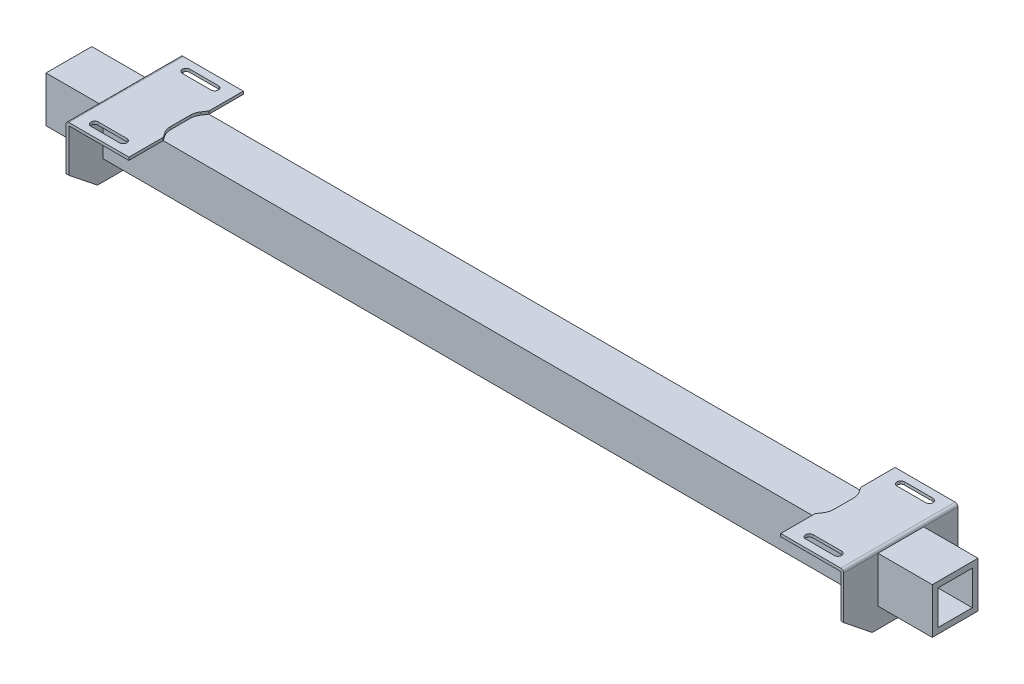
SolidWorks part; units mm, degrees
ref_plane "Front Plane" through (0, 0, 0) normal (0, 0, 1) x (1, 0, 0)
ref_plane "Top Plane" through (0, 0, 0) normal (0, 1, 0) x (1, 0, 0)
ref_plane "Right Plane" through (0, 0, 0) normal (1, 0, 0) x (0, 0, -1)
sketch "Sketch3" plane through (0, 0, 0) normal (1, 0, 0) x (0, 0, -1)
  line L1 (0, 0) -> (80, 0)
  line L2 (0, 0) -> (0, 80)
  line L3 (0, 80) -> (80, 80)
  line L4 (80, 0) -> (80, 80)
  line L5 (10, 70) -> (70, 70)
  line L6 (10, 70) -> (10, 10)
  line L7 (10, 10) -> (70, 10)
  line L8 (70, 70) -> (70, 10)
  dimension "D1" = 80
  dimension "D2" = 80
  dimension "D3" = 10
  dimension "D4" = 10
  dimension "D5" = 10
  dimension "D6" = 10
extrude "Boss-Extrude2" add sketch "Sketch3" along normal blind 1550
ref_plane "Plane1" through (1450, 0, 0) normal (1, 0, 0) x (0, 0, -1)
sketch "Sketch7" plane through (1450, 0, 0) normal (1, 0, 0) x (0, 0, -1)
  line L0 (-60, 85) -> (140, 85)
  line L1 (140, 85) -> (140, 5)
  line L2 (140, 5) -> (90, -35)
  line L3 (90, -35) -> (-10, -35)
  line L4 (-10, -35) -> (-60, 5)
  line L5 (-60, 5) -> (-60, 85)
  line L6 (80, 80) -> (0, 80) construction
  line L7 (70, 70) -> (10, 70) construction
  line L8 (70, 70) -> (10, 70)
  line L9 (70, 10) -> (70, 70) construction
  line L10 (10, 10) -> (70, 10) construction
  line L11 (10, 70) -> (10, 10) construction
  line L12 (70, 10) -> (70, 70)
  line L13 (10, 10) -> (70, 10)
  line L14 (10, 70) -> (10, 10)
  point P10 (40, 85)
  point P11 (40, 80)
  dimension "D1" = 200
  dimension "D2" = 120
  dimension "D3" = 50
  dimension "D4" = 50
  dimension "D5" = 5
  dimension "D6" = 40
extrude "Boss-Extrude3" add sketch "Sketch7" along normal blind 5
sketch "Sketch8" plane through (0, 0, -80) normal (0, 0, -1) x (-1, 0, 0)
  line L0 (-1455, 85) -> (-1450, 85) construction
  line L1 (-1455, 85) -> (-1345, 85)
  line L2 (-1455, 85) -> (-1455, 80)
  line L3 (-1455, 80) -> (-1345, 80)
  line L4 (-1345, 85) -> (-1345, 80)
  line L5 (-1455, 5) -> (-1455, 85) construction
  dimension "D1" = 5
  dimension "D2" = 110
extrude "Boss-Extrude4" add sketch "Sketch8" along normal up to surface and the other way up to surface up to face at (1452.5, 45, -140) other way up to face at (1452.5, 45, 60)
sketch "Sketch9" plane through (0, 85, 0) normal (0, 1, 0) x (1, 0, 0)
  line L0 (1345, 80) -> (1350.8013, 71.2981)
  line L1 (1345, 140) -> (1345, -60) construction
  line L2 (1355, 57.4306) -> (1355, 22.5694)
  line L3 (1350.8013, 8.7019) -> (1345, 0)
  line L4 (1345, 0) -> (0, 0) construction
  line L5 (1345, 0) -> (1345, 80)
  line L6 (1550, 80) -> (1550, 0) construction
  arc A0 (1355, 22.5694) -> (1350.8013, 8.7019) centre (1330, 22.5694) cw
  arc A1 (1350.8013, 71.2981) -> (1355, 57.4306) centre (1330, 57.4306) cw
  point P15 (1355, 15)
  point P18 (1355, 65)
  dimension "D4" = 25
  dimension "D1" = 10
  dimension "D2" = 15
  dimension "D3" = 15
extrude "Cut-Extrude1" cut sketch "Sketch9" against normal up to surface (5 mm away) up to face at (1397.5, 80, 30)
sketch "Sketch10" plane through (0, 85, 0) normal (0, 1, 0) x (1, 0, 0)
  line L0 (1375, 120) -> (1425, 120) construction
  line L1 (1375, 126.5) -> (1425, 126.5)
  line L2 (1375, 113.5) -> (1425, 113.5)
  line L3 (1375, -40) -> (1425, -40) construction
  line L4 (1375, -33.5) -> (1425, -33.5)
  line L5 (1375, -46.5) -> (1425, -46.5)
  line L6 (1455, 140) -> (1345, 140) construction
  arc A0 (1375, 126.5) -> (1375, 113.5) centre (1375, 120) ccw
  arc A1 (1425, 113.5) -> (1425, 126.5) centre (1425, 120) ccw
  arc A2 (1375, -33.5) -> (1375, -46.5) centre (1375, -40) ccw
  arc A3 (1425, -46.5) -> (1425, -33.5) centre (1425, -40) ccw
  point P2 (1400, 120)
  point P7 (1400, -40)
  point P16 (1400, 140)
  point P17 (1400, 126.5)
  dimension "D1" = 50
  dimension "D2" = 13
  dimension "D3" = 13
  dimension "D4" = 160
  dimension "D5" = 20
extrude "Cut-Extrude2" cut sketch "Sketch10" against normal up to next
fillet "Fillet1" radius 5 1 edges at (1455, 85, -40)
ref_plane "Plane2" through (775, 0, 0) normal (1, 0, 0) x (0, 0, -1)
mirror "Mirror1" about plane through (775, 0, 0) normal (1, 0, 0) of "Fillet1", "Boss-Extrude3"
mirror "Mirror2" about plane through (775, 0, 0) normal (1, 0, 0) of "Fillet1", "Cut-Extrude2", "Boss-Extrude3", "Boss-Extrude4", "Cut-Extrude1"
sketch "Sketch13" plane through (0, 0, 0) normal (0, 0, 1) x (1, 0, 0)
  line L0 (0, 40) -> (2446.8223, 40) construction
  line L1 (0, 80) -> (0, 0) construction
sketch "Sketch14" plane through (0, 80, 0) normal (0, 1, 0) x (1, 0, 0)
  line L0 (775, 80) -> (775, 0) construction
  line L1 (1450, 80) -> (100, 80) construction
  line L2 (1450, 0) -> (100, 0) construction
  line L3 (706.4267, 40) -> (843.5733, 40) construction
  point P8 (775, 40)
equation "\"D2@Sketch3\"=\"D1@Sketch3\""
equation "\"D4@Sketch3\"=\"D3@Sketch3\""
equation "\"D5@Sketch3\"=\"D3@Sketch3\""
equation "\"D6@Sketch3\"=\"D3@Sketch3\""
equation "\"D3@Sketch9\"=\"D2@Sketch9\""
